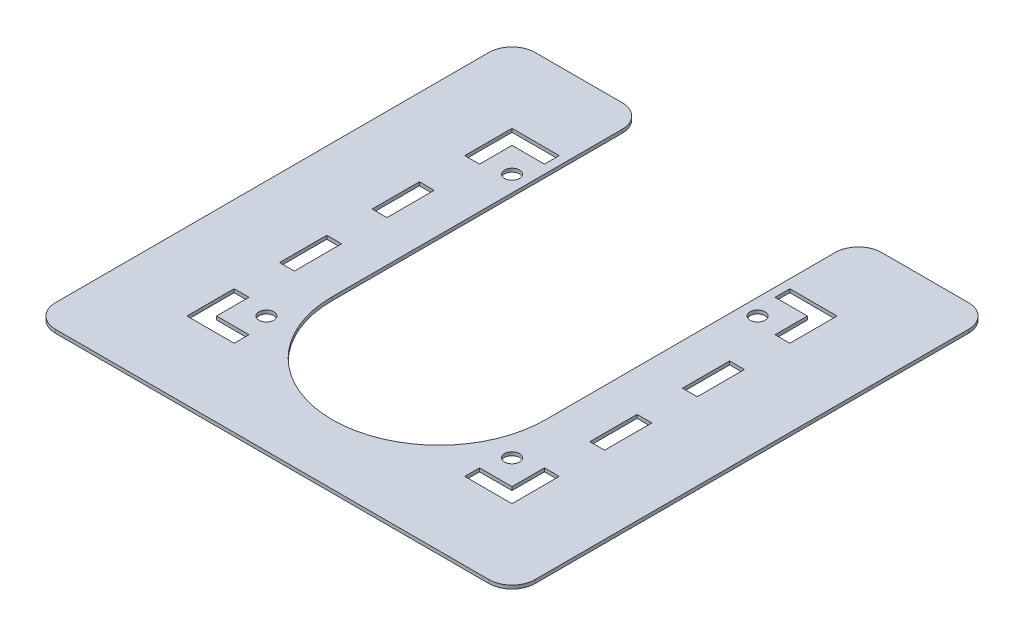
SolidWorks part; units mm, degrees
ref_plane "Front Plane" through (0, 0, 0) normal (0, 0, 1) x (1, 0, 0)
ref_plane "Top Plane" through (0, 0, 0) normal (0, 1, 0) x (1, 0, 0)
ref_plane "Right Plane" through (0, 0, 0) normal (1, 0, 0) x (0, 0, -1)
sketch "Sketch1" plane through (0, 0, 0) normal (0, 1, 0) x (1, 0, 0)
  line L0 (0, 0) -> (0, 21) construction
  line L1 (51.8722, -39.9014) -> (51.8722, 63.843) construction
  line L3 (51.8722, 63.843) -> (-51.8722, 63.843) construction
  line L4 (-51.8722, 63.843) -> (-51.8722, -39.9014) construction
  line L5 (51.8722, -34.9014) -> (51.8722, 58.843)
  line L6 (-46.8722, -39.9014) -> (46.8722, -39.9014)
  line L7 (51.8722, 63.843) -> (-51.8722, 63.843) construction
  line L8 (-51.8722, 58.843) -> (-51.8722, -34.9014)
  line L10 (36.8722, -39.9014) -> (36.8722, 63.843) construction
  line L11 (-36.8722, -39.9014) -> (-36.8722, 63.843) construction
  line L12 (36.8722, -39.9014) -> (36.8722, 63.843) construction
  line L13 (-36.8722, -39.9014) -> (-36.8722, 63.843) construction
  line L14 (23.0585, -3.843) -> (23.0585, 58.843)
  line L15 (-23.0585, -3.843) -> (-23.0585, 58.843)
  line L16 (-46.8722, 63.843) -> (-28.0585, 63.843)
  line L17 (28.0585, 63.843) -> (46.8722, 63.843)
  circle A0 centre (0, 0) radius 21 construction
  circle A1 centre (0, 0) radius 21 construction
  circle A2 centre (26.5585, -14.5877) radius 1.6 construction
  circle A3 centre (-26.5585, -14.5877) radius 1.6 construction
  circle A4 centre (26.5585, 38.5292) radius 1.6 construction
  circle A5 centre (-26.5585, 38.5292) radius 1.6 construction
  circle A6 centre (26.5585, -14.5877) radius 1.6
  circle A7 centre (-26.5585, -14.5877) radius 1.6
  circle A8 centre (26.5585, 38.5292) radius 1.6
  circle A9 centre (-26.5585, 38.5292) radius 1.6
  circle A10 centre (0, -3.843) radius 21.0585 construction
  arc A11 (-21.0585, -3.843) -> (21.0585, -3.843) centre (0, -3.843) ccw construction
  arc A12 (-23.0585, -3.843) -> (23.0585, -3.843) centre (0, -3.843) ccw
  arc A13 (28.0585, 63.843) -> (23.0585, 58.843) centre (28.0585, 58.843) ccw
  circle A14 centre (0, -3.843) radius 23.0585 construction
  arc A15 (-28.0585, 63.843) -> (-23.0585, 58.843) centre (-28.0585, 58.843) cw
  arc A16 (46.8722, 63.843) -> (51.8722, 58.843) centre (46.8722, 58.843) cw
  arc A17 (51.8722, -34.9014) -> (46.8722, -39.9014) centre (46.8722, -34.9014) cw
  arc A18 (-46.8722, -39.9014) -> (-51.8722, -34.9014) centre (-46.8722, -34.9014) cw
  arc A19 (-51.8722, 58.843) -> (-46.8722, 63.843) centre (-46.8722, 58.843) cw
  point P39 (31.0585, -3.843)
  point P42 (23.0585, 63.843)
  point P45 (-23.0585, 63.843)
  dimension "D1" = 2
  dimension "D2" = 5
sketch "Sketch2" plane through (0, 0, 0) normal (0, 0, 1) x (1, 0, 0)
  line L1 (51.8722, -0.75) -> (-51.8722, -0.75)
  line L2 (51.8722, -0.75) -> (51.8722, 0)
  line L3 (51.8722, 0) -> (-51.8722, 0)
  line L4 (-51.8722, -0.75) -> (-51.8722, 0)
extrude "Boss-Extrude1" add sketch "Sketch1" against normal up to vertex (0.75 mm away) up to point (51.8722, -0.75, 0)
sketch "Sketch3" plane through (0, 0, 0) normal (0, 1, 0) x (1, 0, 0)
  line L4 (31.9585, -3.1543) -> (35.1585, -3.1543)
  line L5 (31.9585, 7.0624) -> (31.9585, -3.1543)
  line L6 (35.1585, 7.0624) -> (31.9585, 7.0624)
  line L7 (35.1585, -3.1543) -> (35.1585, 7.0624)
  line L8 (31.9585, -3.1543) -> (35.1585, -3.1543)
  line L9 (31.9585, 7.0624) -> (31.9585, -3.1543)
  line L10 (35.1585, 7.0624) -> (31.9585, 7.0624)
  line L11 (35.1585, -3.1543) -> (35.1585, 7.0624)
  line L12 (35.1585, 16.8791) -> (35.1585, 27.0958)
  line L13 (31.9585, 16.8791) -> (35.1585, 16.8791)
  line L14 (35.1585, 36.9125) -> (35.1585, 47.1292)
  line L15 (35.1585, 47.1292) -> (24.9418, 47.1292)
  line L16 (24.9418, 47.1292) -> (24.9418, 43.9292)
  line L17 (24.9418, 43.9292) -> (31.9585, 43.9292)
  line L18 (31.9585, 43.9292) -> (31.9585, 36.9125)
  line L19 (31.9585, 36.9125) -> (35.1585, 36.9125)
  line L20 (35.1585, 36.9125) -> (35.1585, 47.1292)
  line L21 (35.1585, 47.1292) -> (24.9418, 47.1292)
  line L22 (24.9418, 47.1292) -> (24.9418, 43.9292)
  line L23 (24.9418, 43.9292) -> (31.9585, 43.9292)
  line L24 (31.9585, 43.9292) -> (31.9585, 36.9125)
  line L25 (31.9585, 36.9125) -> (35.1585, 36.9125)
  line L26 (31.9585, 27.0958) -> (31.9585, 16.8791)
  line L27 (35.1585, 27.0958) -> (31.9585, 27.0958)
  line L28 (35.1585, 16.8791) -> (35.1585, 27.0958)
  line L29 (31.9585, 16.8791) -> (35.1585, 16.8791)
  line L30 (31.9585, 27.0958) -> (31.9585, 16.8791)
  line L31 (35.1585, 27.0958) -> (31.9585, 27.0958)
  line L32 (-35.1585, 27.0958) -> (-35.1585, 16.8791)
  line L33 (-35.1585, 16.8791) -> (-31.9585, 16.8791)
  line L34 (-31.9585, 16.8791) -> (-31.9585, 27.0958)
  line L35 (-31.9585, 27.0958) -> (-35.1585, 27.0958)
  line L36 (-35.1585, 27.0958) -> (-35.1585, 16.8791)
  line L37 (-35.1585, 16.8791) -> (-31.9585, 16.8791)
  line L38 (-31.9585, 16.8791) -> (-31.9585, 27.0958)
  line L39 (-31.9585, 27.0958) -> (-35.1585, 27.0958)
  line L40 (-31.9585, 7.0624) -> (-35.1585, 7.0624)
  line L41 (-35.1585, 7.0624) -> (-35.1585, -3.1543)
  line L42 (-31.9585, 36.9125) -> (-31.9585, 43.9292)
  line L43 (-35.1585, 36.9125) -> (-31.9585, 36.9125)
  line L44 (-35.1585, 47.1292) -> (-35.1585, 36.9125)
  line L45 (-24.9418, 47.1292) -> (-35.1585, 47.1292)
  line L46 (-24.9418, 43.9292) -> (-24.9418, 47.1292)
  line L47 (-31.9585, 43.9292) -> (-24.9418, 43.9292)
  line L48 (-31.9585, 36.9125) -> (-31.9585, 43.9292)
  line L49 (-35.1585, 36.9125) -> (-31.9585, 36.9125)
  line L50 (-35.1585, 47.1292) -> (-35.1585, 36.9125)
  line L51 (-24.9418, 47.1292) -> (-35.1585, 47.1292)
  line L52 (-24.9418, 43.9292) -> (-24.9418, 47.1292)
  line L53 (-31.9585, 43.9292) -> (-24.9418, 43.9292)
  line L54 (31.9585, -12.971) -> (31.9585, -19.9877)
  line L55 (35.1585, -12.971) -> (31.9585, -12.971)
  line L56 (35.1585, -23.1877) -> (35.1585, -12.971)
  line L57 (24.9418, -23.1877) -> (35.1585, -23.1877)
  line L58 (24.9418, -19.9877) -> (24.9418, -23.1877)
  line L59 (31.9585, -19.9877) -> (24.9418, -19.9877)
  line L60 (31.9585, -12.971) -> (31.9585, -19.9877)
  line L61 (35.1585, -12.971) -> (31.9585, -12.971)
  line L62 (35.1585, -23.1877) -> (35.1585, -12.971)
  line L63 (24.9418, -23.1877) -> (35.1585, -23.1877)
  line L64 (24.9418, -19.9877) -> (24.9418, -23.1877)
  line L65 (31.9585, -19.9877) -> (24.9418, -19.9877)
  line L66 (-35.1585, -12.971) -> (-35.1585, -23.1877)
  line L67 (-35.1585, -23.1877) -> (-24.9418, -23.1877)
  line L68 (-24.9418, -23.1877) -> (-24.9418, -19.9877)
  line L69 (-24.9418, -19.9877) -> (-31.9585, -19.9877)
  line L70 (-31.9585, -19.9877) -> (-31.9585, -12.971)
  line L71 (-31.9585, -12.971) -> (-35.1585, -12.971)
  line L72 (-35.1585, -12.971) -> (-35.1585, -23.1877)
  line L73 (-35.1585, -23.1877) -> (-24.9418, -23.1877)
  line L74 (-24.9418, -23.1877) -> (-24.9418, -19.9877)
  line L75 (-24.9418, -19.9877) -> (-31.9585, -19.9877)
  line L76 (-31.9585, -19.9877) -> (-31.9585, -12.971)
  line L77 (-31.9585, -12.971) -> (-35.1585, -12.971)
  line L78 (-35.1585, -3.1543) -> (-31.9585, -3.1543)
  line L79 (-31.9585, -3.1543) -> (-31.9585, 7.0624)
  line L80 (-31.9585, 7.0624) -> (-35.1585, 7.0624)
  line L81 (-35.1585, 7.0624) -> (-35.1585, -3.1543)
  line L82 (-35.1585, -3.1543) -> (-31.9585, -3.1543)
  line L83 (-31.9585, -3.1543) -> (-31.9585, 7.0624)
  dimension "D1" = 0
  dimension "D2" = 0
  dimension "D3" = 0
  dimension "D4" = 0
  dimension "D5" = 0
  dimension "D6" = 0
  dimension "D7" = 0
  dimension "D8" = 0
extrude "Cut-Extrude1" cut sketch "Sketch3" against normal through all
